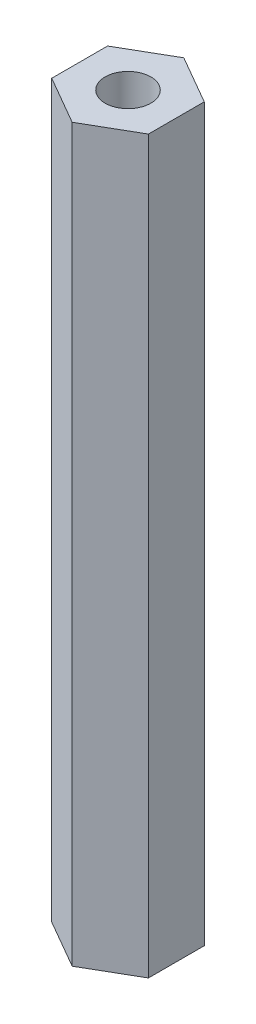
SolidWorks part; units mm, degrees
ref_plane "Alzado" through (0, 0, 0) normal (0, 0, 1) x (1, 0, 0)
ref_plane "Planta" through (0, 0, 0) normal (0, 1, 0) x (1, 0, 0)
ref_plane "Vista lateral" through (0, 0, 0) normal (1, 0, 0) x (0, 0, -1)
sketch "Croquis1" plane through (0, 0, 0) normal (0, 1, 0) x (1, 0, 0)
  line L1 (0, 3.6662) -> (-3.175, 1.8331)
  line L2 (-3.175, 1.8331) -> (-3.175, -1.8331)
  line L3 (-3.175, -1.8331) -> (0, -3.6662)
  line L4 (0, -3.6662) -> (3.175, -1.8331)
  line L5 (3.175, -1.8331) -> (3.175, 1.8331)
  line L6 (3.175, 1.8331) -> (0, 3.6662)
  circle A0 centre (0, 0) radius 3.175 construction
  dimension "D1" = 6.35
extrude "Saliente-Extruir1" add sketch "Croquis1" along normal blind 48
sketch "Croquis2" plane through (0, 48, 0) normal (0, 1, 0) x (1, 0, 0)
  circle A0 centre (0, 0) radius 1.5
  dimension "D1" = 3
extrude "Cortar-Extruir1" cut sketch "Croquis2" against normal blind 10
extrude "Cortar-Extruir2" cut sketch "Croquis2<2>" against normal blind 10 from offset 38
sketch "Croquis2<2>" plane through (0, 48, 0) normal (0, 1, 0) x (1, 0, 0) same geometry as "Croquis2"
